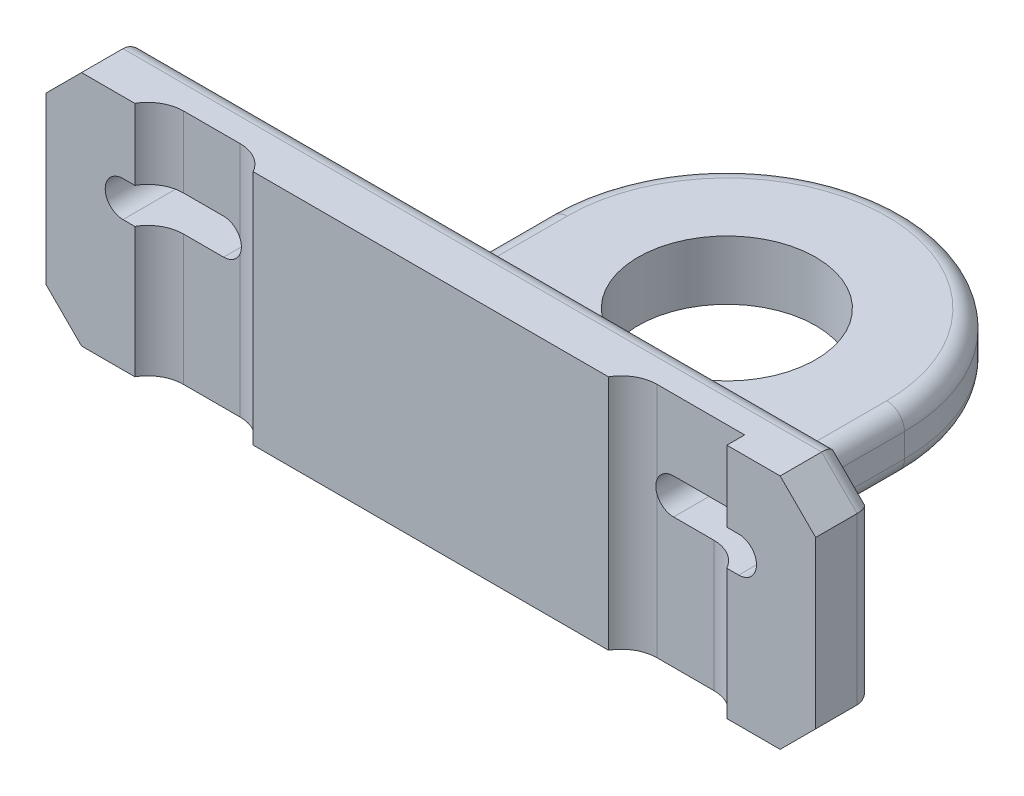
SolidWorks part; units mm, degrees
ref_plane "Plan de face" through (0, 0, 0) normal (0, 0, 1) x (1, 0, 0)
ref_plane "Plan de dessus" through (0, 0, 0) normal (0, 1, 0) x (1, 0, 0)
ref_plane "Plan de droite" through (0, 0, 0) normal (1, 0, 0) x (0, 0, -1)
sketch "Esquisse1" plane through (0, 0, 0) normal (0, 0, 1) x (1, 0, 0)
  line L1 (-51.8393, 0) -> (78.1607, 0)
  line L2 (-51.8393, 0) -> (-51.8393, 40)
  line L3 (-51.8393, 40) -> (78.1607, 40)
  line L4 (78.1607, 0) -> (78.1607, 40)
  dimension "D1" = 130
  dimension "D2" = 40
extrude "Base" add sketch "Esquisse1" along normal blind 10
chamfer "Chanfrein1" distance 6 angle 45 1 edges at (78.1607, 0, 5)
chamfer "Chanfrein2" distance 6 angle 45 3 edges at (-51.8393, 40, 5) (-51.8393, 0, 5) (78.1607, 40, 5)
sketch "languette" plane through (0, 0, 0) normal (0, 1, 0) x (1, 0, 0)
  line L0 (-16.8393, -10) -> (-16.8393, 40)
  line L1 (72.1607, -10) -> (-45.8393, -10) construction
  line L2 (43.1607, 40) -> (43.1607, -10)
  line L3 (43.1607, -10) -> (-16.8393, -10)
  line L7 (-51.8393, -10) -> (-51.8393, 0) construction
  arc A0 (-16.8393, 40) -> (43.1607, 40) centre (13.1607, 40) cw
  point P9 (-51.8393, -5.0494)
  point P10 (-51.8393, -5)
  dimension "D1" = 30
  dimension "D2" = 50
  dimension "D3" = 65
extrude "Languette_Ext" add sketch "languette" along normal blind 10
hole_wizard "Dégagement M31" positions "Esquisse3" profile "Esquisse4" hole size "M3" standard "AS" end condition up to next
sketch "Esquisse3" plane through (0, 0, 0) normal (0, -1, 0) x (-1, 0, 0)
  point P0 (-13.1607, 40)
sketch "Esquisse4" plane through (13.1607, 0, -40) normal (1, 0, 0) x (0, 0, -1)
  line L0 (0, 0) -> (0, 10)
  line L1 (0, 10) -> (15, 10)
  line L2 (15, 10) -> (15, 0)
  line L5 (15, 0) -> (0, 0)
  line L11 (0, -6.35) -> (0, 107.95) construction
  dimension "Diamètre du perçage jusqu'au prochain" = 30
  dimension "Profondeur du perçage jusqu'au prochain" = 10
sketch "Esquisse5" plane through (0, 0, 0) normal (0, -1, 0) x (1, 0, 0)
  line L0 (-45.8393, 10) -> (72.1607, 10) construction
  line L1 (43.1607, 10) -> (63.1607, 10)
  line L2 (43.1607, 10) -> (43.1607, 7)
  line L3 (43.1607, 7) -> (63.1607, 7)
  line L4 (63.1607, 10) -> (63.1607, 7)
  dimension "D1" = 3
  dimension "D2" = 20
extrude "Enlèv. mat.-Extru.1" cut sketch "Esquisse5" against normal up to next
sketch "Esquisse6" plane through (0, 0, 0) normal (0, -1, 0) x (-1, 0, 0)
  line L0 (-13.1607, 76.1806) -> (-13.1607, -17.6364) construction
ref_plane "Plan1" through (13.1607, 0, 0) normal (1, 0, 0) x (0, 0, -1)
mirror "Symétrie1" about plane through (13.1607, 0, 0) normal (1, 0, 0) of "Enlèv. mat.-Extru.1"
sketch "Esquisse7" plane through (0, 0, 0) normal (0, 0, -1) x (-1, 0, 0)
  line L0 (-65.1607, 25) -> (-51.1607, 25) construction
  line L1 (-65.1607, 28) -> (-51.1607, 28)
  line L2 (-65.1607, 22) -> (-51.1607, 22)
  line L3 (-72.1607, 40) -> (45.8393, 40) construction
  line L4 (-78.1607, 6) -> (-78.1607, 34) construction
  arc A0 (-65.1607, 28) -> (-65.1607, 22) centre (-65.1607, 25) ccw
  arc A1 (-51.1607, 22) -> (-51.1607, 28) centre (-51.1607, 25) ccw
  point P2 (-58.1607, 25)
  point P7 (-68.1607, 25)
  point P8 (-48.1607, 25)
  dimension "D1" = 6
  dimension "D2" = 20
  dimension "D3" = 15
  dimension "D4" = 20
extrude "Rainure" cut sketch "Esquisse7" against normal up to next
mirror "Symétrie2" about plane through (13.1607, 0, 0) normal (1, 0, 0) of "Rainure"
fillet "Conges3mm" radius 3 18 edges at (-16.8393, 10, -20) (13.1607, 10, -70) (-16.8393, 0, -20) (13.1607, 0, -70) (43.1607, 10, -20) (43.1607, 0, -20) (-48.8393, 3, 0) (-51.8393, 20, 0) (-48.8393, 37, 0) (13.1607, 40, 0) (75.1607, 37, 0) (78.1607, 20, 0) (75.1607, 3, 0) (57.6607, 0, 0) (-31.3393, 0, 0) (-16.8393, 5, 0) (43.1607, 5, 0) (13.1607, 10, 0)
fillet "Conges6mm" radius 6 5 edges at (-36.8393, 34, 7) (-36.8393, 11, 7) (-16.8393, 20, 7) (43.1607, 20, 7) (63.1607, 11, 7)
